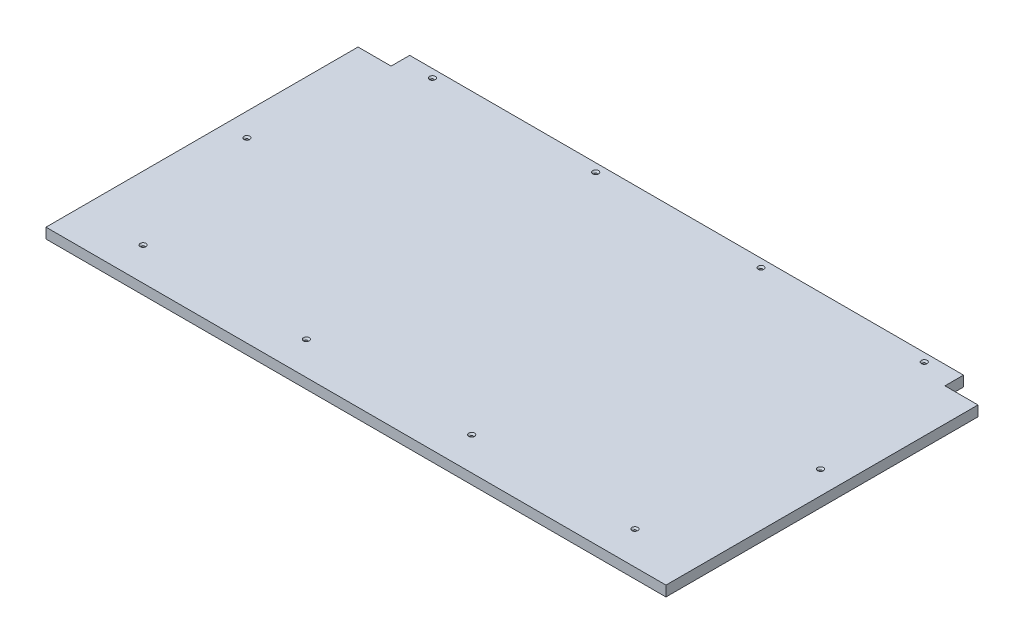
SolidWorks part; units mm, degrees
material "Cedar"
ref_plane "Front Plane" through (0, 0, 0) normal (0, 0, 1) x (1, 0, 0)
ref_plane "Top Plane" through (0, 0, 0) normal (0, 1, 0) x (1, 0, 0)
ref_plane "Right Plane" through (0, 0, 0) normal (1, 0, 0) x (0, 0, -1)
sketch "Sketch1" plane through (0, 0, 0) normal (0, 1, 0) x (1, 0, 0)
  line L1 (750, -400) -> (-750, -400)
  line L2 (750, -400) -> (750, 400)
  line L3 (750, 400) -> (-750, 400)
  line L4 (-750, -400) -> (-750, 400)
  line L5 (750, -400) -> (-750, 400) construction
  line L6 (750, 400) -> (-750, -400) construction
  point P0 (0, 0)
  dimension "D1" = 800
  dimension "D2" = 1500
extrude "RawMaterial" add sketch "Sketch1" along normal blind 25
sketch "Sketch2" plane through (0, 25, 0) normal (0, 1, 0) x (1, 0, 0)
  line L0 (750, 400) -> (-750, 400) construction
  line L1 (-761.4719, 422.6992) -> (-670, 422.6992)
  line L2 (-761.4719, 422.6992) -> (-761.4719, 355)
  line L3 (-761.4719, 355) -> (-670, 355)
  line L4 (-670, 422.6992) -> (-670, 355)
  line L5 (777.3454, 416.3957) -> (670, 416.3957)
  line L6 (777.3454, 416.3957) -> (777.3454, 355)
  line L7 (777.3454, 355) -> (670, 355)
  line L8 (670, 416.3957) -> (670, 355)
  line L9 (-750, 400) -> (-750, -400) construction
  line L10 (750, -400) -> (750, 400) construction
  line M5 (-750, 400) -> (-750, -400)
  line M7 (750, -400) -> (750, 400)
  line M8 (750, 400) -> (-750, 400)
  dimension "D1" = 45
  dimension "D2" = 80
  dimension "D3" = 80
extrude "SlotsForFrame" cut sketch "Sketch2" against normal through all contours L4 L3 M8 M5 | L8 L7 M8 M7 region at (710, 25, -377.5) region at (-710, 25, -377.5)
hole_wizard "M6 Clearance Hole1" positions "Sketch4" profile "Sketch5" hole size "M6" standard "ANSI Metric" end condition through all
sketch "Sketch4" plane through (0, 25, 0) normal (0, -1, 0) x (-1, 0, 0)
  line L0 (750, -400) -> (-750, -400) construction
  line L1 (750, 355) -> (750, -400) construction
  line L2 (-750, -400) -> (-750, 355) construction
  point P0 (-595, -320)
  point P2 (-200, -320)
  point P4 (200, -320)
  point P6 (595, -320)
  point P10 (694, 30)
  point P14 (-694, 30)
  point P16 (-595, 380)
  point P18 (-200, 380)
  point P20 (200, 380)
  point P22 (595, 380)
  point P44 (0, 0)
  point P45 (0, 0)
  dimension "D1" = 80
  dimension "D2" = 155
  dimension "D3" = 155
  dimension "D4" = 395
  dimension "D5" = 400
  dimension "D6" = 780
  dimension "D7" = 56
  dimension "D8" = 1444
  dimension "D9" = 350
sketch "Sketch5" plane through (595, 25, 320) normal (1, 0, 0) x (0, 0, 1)
  line L0 (0, 0) -> (0, 25)
  line L1 (0, 25) -> (3.3, 25)
  line L2 (3.3, 25) -> (3.3, 3.7)
  line L3 (3.3, 3.7) -> (7, 0)
  line L5 (7, 0) -> (0, 0)
  line L6 (-3.3, 3.7) -> (-7, 0) construction
  line L11 (0, -6.35) -> (0, 107.95) construction
  dimension "Thru Hole Dia." = 6.6
  dimension "Thru Hole Depth" = 25
  dimension "Near C'Sink Dia." = 14
  dimension "Near C'Sink Angle" = 90
equation "\"D3@Sketch2\"=\"D2@Sketch2\""
equation "\"TableThickness\"= \"Thickness@RawMaterial\""
equation "\"D3@Sketch4\"=\"D2@Sketch4\""
